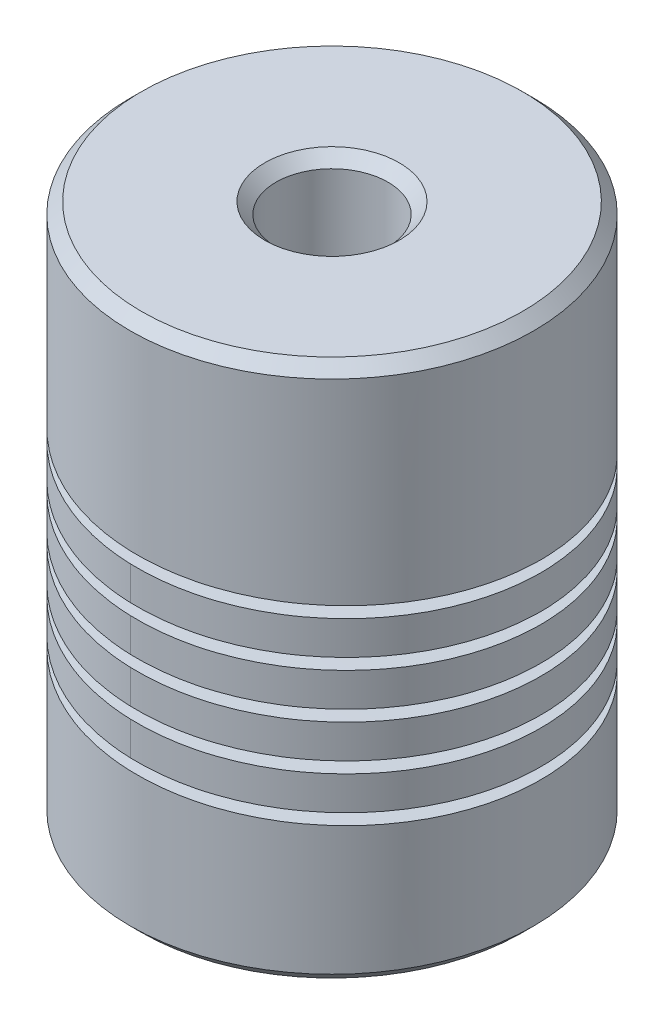
SolidWorks part; units mm, degrees
ref_plane "Front Plane" through (0, 0, 0) normal (0, 0, 1) x (1, 0, 0)
ref_plane "Top Plane" through (0, 0, 0) normal (0, 1, 0) x (1, 0, 0)
ref_plane "Right Plane" through (0, 0, 0) normal (1, 0, 0) x (0, 0, -1)
sketch "Sketch1" plane through (0, 0, 0) normal (0, 1, 0) x (1, 0, 0)
  circle A0 centre (0, 0) radius 9
  dimension "D1" = 18
extrude "Boss-Extrude1" add sketch "Sketch1" along normal blind 24
sketch "Sketch2" plane through (0, 24, 0) normal (0, 1, 0) x (1, 0, 0)
  circle A0 centre (0, 0) radius 2.5
  dimension "D1" = 5
extrude "Cut-Extrude1" cut sketch "Sketch2" against normal through all
sketch "Sketch3" plane through (0, 0, 0) normal (0, -1, 0) x (1, 0, 0)
  circle A0 centre (0, 0) radius 4
  dimension "D1" = 8
extrude "Cut-Extrude2" cut sketch "Sketch3" against normal offset from surface (16 mm away) 8 up to face at (0, 24, 2.5)
chamfer "Chamfer1" distance 0.5 angle 45 4 edges at (0, 24, 2.5) (0, 24, 9) (0, 0, 9) (0, 0, -4)
sketch "Sketch10" plane through (0, 16, 0) normal (0, -1, 0) x (1, 0, 0)
  line L0 (0, -9) -> (0, -4) construction
  line L1 (0, -9) -> (0, -4) construction
  circle A0 centre (0, 0) radius 6.5
  circle A1 centre (0, 0) radius 4 construction
  circle A2 centre (0, 0) radius 9 construction
  point P10 (0, -6.5)
curve "Helix/Spiral1" pitch 2 height 10 turns 5
sketch "Sketch8" plane through (0, 0, 0) normal (1, 0, 0) x (0, 0, -1)
  line L0 (9, 0.5) -> (9, 23.5) construction
  line L1 (9, 16) -> (4, 16)
  line L2 (9, 16) -> (9, 15.5)
  line L3 (9, 15.5) -> (4, 15.5)
  line L4 (4, 16) -> (4, 15.5)
  line L5 (4, 0.5) -> (4, 16) construction
  line L6 (4, 0.5) -> (4, 16) construction
  line L8 (9, 0.5) -> (9, 23.5) construction
  line L9 (4, 15.5) -> (9, 16) construction
  line L10 (-4, 16) -> (4, 16) construction
  dimension "D2" = 0.5
sweep "Cut-Sweep2" cut profiles "Sketch8" path "Helix/Spiral1"
